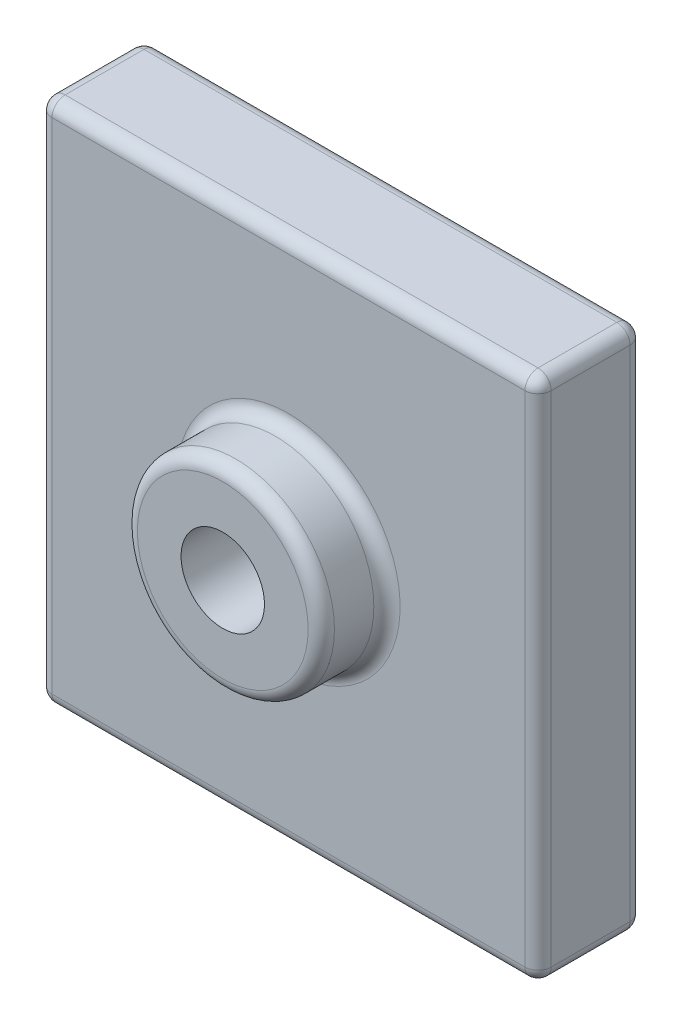
SolidWorks part; units mm, degrees
ref_plane "Front Plane" through (0, 0, 0) normal (0, 0, 1) x (1, 0, 0)
ref_plane "Top Plane" through (0, 0, 0) normal (0, 1, 0) x (1, 0, 0)
ref_plane "Right Plane" through (0, 0, 0) normal (1, 0, 0) x (0, 0, -1)
sketch "Sketch1" plane through (0, 0, 0) normal (0, 0, 1) x (1, 0, 0)
  line L1 (0, 0) -> (38, 0)
  line L2 (0, 0) -> (0, 40)
  line L3 (0, 40) -> (38, 40)
  line L4 (38, 0) -> (38, 40)
  dimension "D1" = 38
  dimension "D2" = 40
extrude "Boss-Extrude1" add sketch "Sketch1" along normal blind 8
sketch "Sketch2" plane through (0, 0, 8) normal (0, 0, 1) x (1, 0, 0)
  line L4 (0, 40) -> (0, 0)
  line L5 (0, 0) -> (38, 0)
  line L6 (38, 0) -> (38, 40)
  line L7 (38, 40) -> (0, 40)
  line L8 (0, 40) -> (0, 0) construction
  line L9 (0, 0) -> (38, 0) construction
  line L10 (38, 0) -> (38, 40) construction
  line L11 (38, 40) -> (0, 40) construction
  circle A0 centre (19, 20) radius 7.5
  circle A1 centre (19, 20) radius 3.175
  point P2 (19, 20)
  point P4 (0, 20)
  point P6 (19, 0)
  dimension "D2" = 15
  dimension "D3" = 6.35
  dimension "D1" = 0
extrude "Boss-Extrude2" add sketch "Sketch2" along normal blind 5
fillet "Fillet1" radius 1 14 edges at (26.5, 20, 13) (19, 0, 0) (19, 40, 0) (38, 0, 4) (38, 40, 4) (38, 20, 0) (0, 40, 4) (0, 0, 4) (0, 20, 0) (26.5, 20, 8) (19, 40, 8) (38, 20, 8) (19, 0, 8) (0, 20, 8)
sketch "Sketch3" plane through (0, 0, 0) normal (0, 0, -1) x (-1, 0, 0)
  line L4 (-1, 39) -> (-37, 39)
  line L5 (-37, 39) -> (-37, 1)
  line L6 (-37, 1) -> (-1, 1)
  line L7 (-1, 1) -> (-1, 39)
  line L8 (-1, 39) -> (-37, 39) construction
  line L9 (-37, 39) -> (-37, 1) construction
  line L10 (-37, 1) -> (-1, 1) construction
  line L11 (-1, 1) -> (-1, 39) construction
  line L15 (-17.1669, 23.175) -> (-20.8331, 23.175)
  line L16 (-20.8331, 23.175) -> (-22.6662, 20)
  line L17 (-22.6662, 20) -> (-20.8331, 16.825)
  line L18 (-20.8331, 16.825) -> (-17.1669, 16.825)
  line L19 (-17.1669, 16.825) -> (-15.3338, 20)
  line L20 (-15.3338, 20) -> (-17.1669, 23.175)
  circle A0 centre (-19, 20) radius 3.175 construction
  point P2 (-19, 39)
  point P4 (-37, 20)
  point P6 (-19, 20)
  dimension "D2" = 6.35
  dimension "D1" = 0
extrude "Cut-Extrude1" cut sketch "Sketch3" against normal blind 5.5562
sketch "Sketch4" plane through (0, 0, 0) normal (0, 0, -1) x (-1, 0, 0)
  circle A0 centre (-19, 20) radius 3.175 construction
  circle A1 centre (-19, 20) radius 3.175
extrude "Cut-Extrude2" cut sketch "Sketch4" against normal through all
